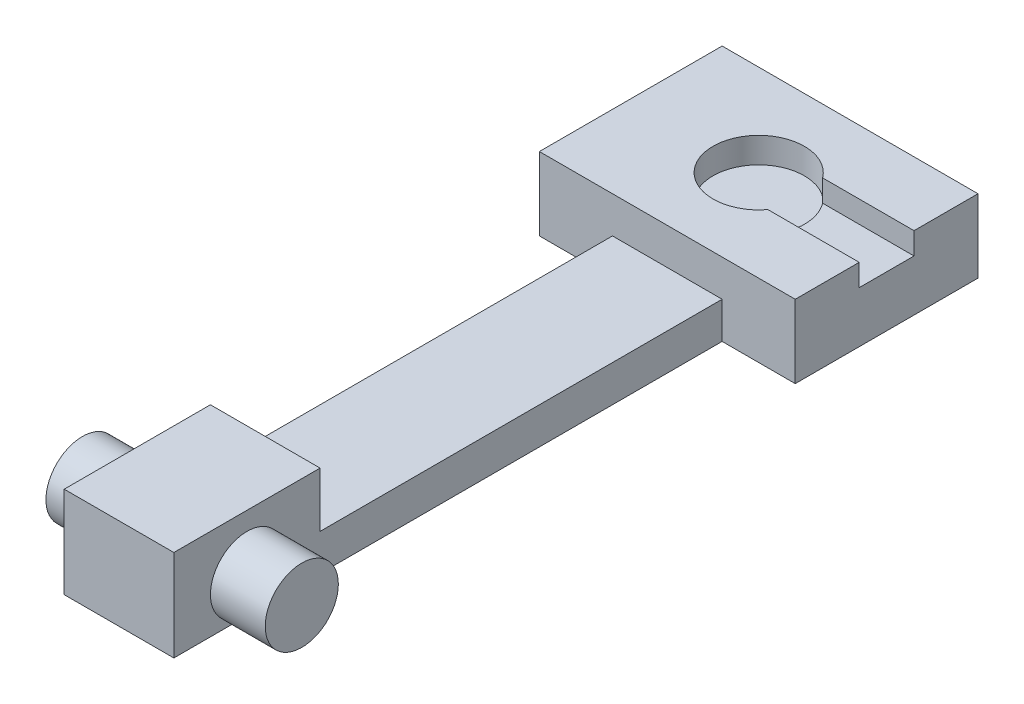
SolidWorks part; units mm, degrees
ref_plane "Front Plane" through (0, 0, 0) normal (0, 0, 1) x (1, 0, 0)
ref_plane "Top Plane" through (0, 0, 0) normal (0, 1, 0) x (1, 0, 0)
ref_plane "Right Plane" through (0, 0, 0) normal (1, 0, 0) x (0, 0, -1)
sketch "Sketch1" plane through (0, 0, 0) normal (0, 1, 0) x (1, 0, 0)
  line L0 (0, 0) -> (30, 0)
  line L1 (30, 0) -> (30, 150)
  line L2 (0, 0) -> (0, 150)
  line L4 (0, 150) -> (-20, 150)
  line L5 (-20, 150) -> (-20, 200)
  line L6 (-20, 200) -> (50, 200)
  line L7 (50, 200) -> (50, 150)
  line L8 (50, 150) -> (30, 150)
  dimension "D1" = 150
  dimension "D2" = 30
  dimension "D3" = 20
  dimension "D4" = 50
extrude "Boss-Extrude1" add sketch "Sketch1" along normal blind 20
sketch "Sketch2" plane through (0, 20, 0) normal (0, 1, 0) x (1, 0, 0)
  line L1 (0, 0) -> (30, 0) construction
  line L2 (15, 0) -> (15, 200) construction
  line L3 (50, 200) -> (-20, 200) construction
  line L4 (50, 175) -> (-20, 175) construction
  line L5 (50, 150) -> (50, 200) construction
  line L6 (-20, 200) -> (-20, 150) construction
  circle A0 centre (15, 175) radius 12.5
  point P14 (15, 111.206)
  dimension "D1" = 25
extrude "Cut-Extrude1" cut sketch "Sketch2" against normal blind 7
sketch "Sketch3" plane through (0, 20, 0) normal (0, 1, 0) x (1, 0, 0)
  line L0 (50, 150) -> (50, 200) construction
  line L1 (50, 182.5) -> (12, 182.5)
  line L2 (50, 182.5) -> (50, 167.5)
  line L3 (50, 167.5) -> (12, 167.5)
  line L4 (12, 182.5) -> (12, 167.5)
  line L5 (30, 150) -> (50, 150) construction
  dimension "D1" = 17.5
  dimension "D2" = 15
  dimension "D3" = 38
extrude "Cut-Extrude2" cut sketch "Sketch3" against normal blind 6
sketch "Sketch7" plane through (0, 20, 0) normal (0, 1, 0) x (1, 0, 0)
  line L0 (0, 150) -> (0, 0) construction
  line L1 (30, 0) -> (0, 0)
  line L2 (30, 0) -> (30, 40)
  line L3 (30, 40) -> (0, 40)
  line L4 (0, 0) -> (0, 40)
  dimension "D1" = 40
extrude "Boss-Extrude2" add sketch "Sketch7" along normal blind 5
sketch "Sketch8" plane through (30, 0, 0) normal (1, 0, 0) x (0, 0, -1)
  line L0 (20, 25) -> (20, 0) construction
  line L1 (0, 25) -> (40, 25) construction
  line L2 (0, 0) -> (150, 0) construction
  line L3 (0, 10) -> (38.6017, 10) construction
  line L6 (38.5, 0) -> (-38.5, 0) construction
  circle A0 centre (20, 10) radius 10
  point P12 (0, 0)
  point P13 (0, 0)
  point P14 (20, 12.8134)
  dimension "D1" = 20
  dimension "D2" = 10
extrude "Boss-Extrude3" add sketch "Sketch8" along normal blind 15 and the other way blind 45
sketch "Sketch9" plane through (0, 20, 0) normal (0, 1, 0) x (1, 0, 0)
  line L0 (0, -11) -> (0, 11) construction
  line L1 (30, 150) -> (0, 150)
  line L2 (30, 150) -> (30, 40)
  line L3 (30, 40) -> (0, 40)
  line L4 (0, 150) -> (0, 40)
  line L5 (30, 40) -> (0, 40) construction
extrude "Cut-Extrude3" cut sketch "Sketch9" against normal blind 10
